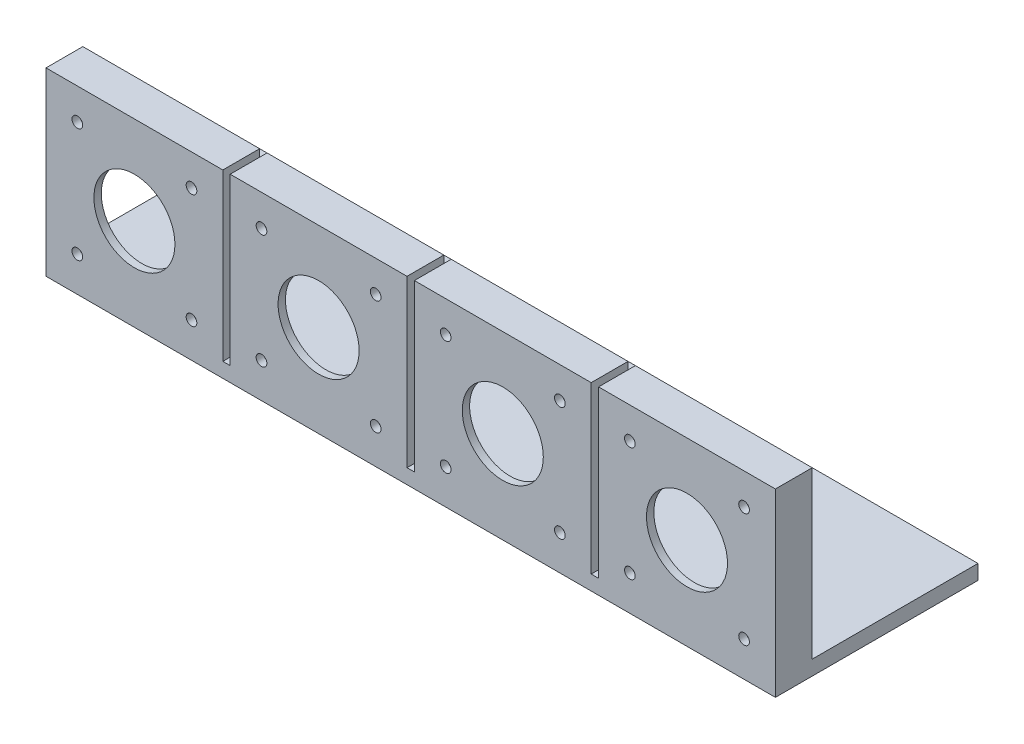
SolidWorks part; units mm, degrees
ref_plane "Спереди" through (0, 0, 0) normal (0, 0, 1) x (1, 0, 0)
ref_plane "Сверху" through (0, 0, 0) normal (0, 1, 0) x (1, 0, 0)
ref_plane "Справа" through (0, 0, 0) normal (1, 0, 0) x (0, 0, -1)
sketch "Эскиз1" plane through (0, 0, 0) normal (0, 0, 1) x (1, 0, 0)
  line L0 (-1000, 0) -> (49000, 0) construction
  line L1 (-21, -21) -> (21, -21)
  line L2 (-21, -21) -> (-21, 21)
  line L3 (-21, 21) -> (21, 21)
  line L4 (21, -21) -> (21, 21)
  line L5 (-21, -21) -> (21, 21) construction
  line L6 (-21, 21) -> (21, -21) construction
  line L7 (-24, -24) -> (24, -24)
  line L8 (-24, -24) -> (-24, 24)
  line L9 (-24, 24) -> (24, 24)
  line L10 (24, -24) -> (24, 24)
  line L11 (-24, -24) -> (24, 24) construction
  line L12 (-24, 24) -> (24, -24) construction
  line L13 (29, -21) -> (71, -21)
  line L14 (29, -21) -> (29, 21)
  line L15 (29, 21) -> (71, 21)
  line L16 (71, -21) -> (71, 21)
  line L17 (26, -24) -> (74, -24)
  line L18 (26, -24) -> (26, 24)
  line L19 (26, 24) -> (74, 24)
  line L20 (74, -24) -> (74, 24)
  line L21 (29, -21) -> (71, 21) construction
  line L22 (29, 21) -> (71, -21) construction
  line L23 (26, -24) -> (74, 24) construction
  line L24 (26, 24) -> (74, -24) construction
  line L25 (79, -21) -> (121, -21)
  line L26 (79, -21) -> (79, 21)
  line L27 (79, 21) -> (121, 21)
  line L28 (121, -21) -> (121, 21)
  line L29 (76, -24) -> (124, -24)
  line L30 (76, -24) -> (76, 24)
  line L31 (76, 24) -> (124, 24)
  line L32 (124, -24) -> (124, 24)
  line L33 (79, -21) -> (121, 21) construction
  line L34 (79, 21) -> (121, -21) construction
  line L35 (76, -24) -> (124, 24) construction
  line L36 (76, 24) -> (124, -24) construction
  line L37 (129, -21) -> (171, -21)
  line L38 (129, -21) -> (129, 21)
  line L39 (129, 21) -> (171, 21)
  line L40 (171, -21) -> (171, 21)
  line L41 (126, -24) -> (174, -24)
  line L42 (126, -24) -> (126, 24)
  line L43 (126, 24) -> (174, 24)
  line L44 (174, -24) -> (174, 24)
  line L45 (129, -21) -> (171, 21) construction
  line L46 (129, 21) -> (171, -21) construction
  line L47 (126, -24) -> (174, 24) construction
  line L48 (126, 24) -> (174, -24) construction
  point P0 (0, 0)
  point P5 (0, 0)
  point P14 (50, 0)
  point P19 (50, 0)
  point P24 (100, 0)
  point P29 (100, 0)
  point P34 (150, 0)
  point P39 (150, 0)
  dimension "D1" = 42
  dimension "D2" = 48
  dimension "D3" = 3
  dimension "D4" = 42
  dimension "D6" = 2
  dimension "D5" = 4
extrude "Бобышка-Вытянуть1" add sketch "Эскиз1" along normal blind 10
sketch "Эскиз2" plane through (0, 0, 10) normal (0, 0, 1) x (1, 0, 0)
  line L0 (-1000, 0) -> (49000, 0) construction
  line L1 (-21, 21) -> (21, 21)
  line L2 (-21, 21) -> (-21, -21)
  line L3 (-21, -21) -> (21, -21)
  line L4 (21, 21) -> (21, -21)
  line L5 (-21, 21) -> (21, -21) construction
  line L6 (-21, -21) -> (21, 21) construction
  line L7 (29, 21) -> (71, 21)
  line L8 (29, 21) -> (29, -21)
  line L9 (29, -21) -> (71, -21)
  line L10 (71, 21) -> (71, -21)
  line L11 (29, 21) -> (71, -21) construction
  line L12 (29, -21) -> (71, 21) construction
  line L13 (79, 21) -> (121, 21)
  line L14 (79, 21) -> (79, -21)
  line L15 (79, -21) -> (121, -21)
  line L16 (121, 21) -> (121, -21)
  line L17 (79, 21) -> (121, -21) construction
  line L18 (79, -21) -> (121, 21) construction
  line L19 (129, 21) -> (171, 21)
  line L20 (129, 21) -> (129, -21)
  line L21 (129, -21) -> (171, -21)
  line L22 (171, 21) -> (171, -21)
  line L23 (129, 21) -> (171, -21) construction
  line L24 (129, -21) -> (171, 21) construction
  circle A0 centre (-15.5, 15.5) radius 1.45
  circle A1 centre (15.5, 15.5) radius 1.45
  circle A2 centre (15.5, -15.5) radius 1.45
  circle A3 centre (-15.5, -15.5) radius 1.45
  circle A4 centre (34.5, 15.5) radius 1.45
  circle A5 centre (65.5, 15.5) radius 1.45
  circle A6 centre (65.5, -15.5) radius 1.45
  circle A7 centre (34.5, -15.5) radius 1.45
  circle A8 centre (84.5, 15.5) radius 1.45
  circle A9 centre (115.5, 15.5) radius 1.45
  circle A10 centre (115.5, -15.5) radius 1.45
  circle A11 centre (84.5, -15.5) radius 1.45
  circle A12 centre (134.5, 15.5) radius 1.45
  circle A13 centre (165.5, 15.5) radius 1.45
  circle A14 centre (165.5, -15.5) radius 1.45
  circle A15 centre (134.5, -15.5) radius 1.45
  circle A16 centre (0, 0) radius 11
  circle A17 centre (50, 0) radius 11
  circle A18 centre (100, 0) radius 11
  circle A19 centre (150, 0) radius 11
  point P4 (0, 0)
  point P12 (0, 0)
  point P15 (0, 0)
  point P18 (0, 0)
  point P21 (0, 0)
  point P27 (50, 0)
  point P30 (50, 0)
  point P33 (50, 0)
  point P36 (50, 0)
  point P39 (50, 0)
  point P44 (100, 0)
  point P47 (100, 0)
  point P50 (100, 0)
  point P53 (100, 0)
  point P56 (100, 0)
  point P61 (150, 0)
  point P64 (150, 0)
  point P67 (150, 0)
  point P70 (150, 0)
  point P73 (150, 0)
  dimension "D1" = 5.5
  dimension "D2" = 2.9
  dimension "D3" = 4
  dimension "D6" = 22
  dimension "D5" = 8
  dimension "D4" = 4
extrude "Бобышка-Вытянуть2" add sketch "Эскиз2" against normal blind 2
sketch "Эскиз3" plane through (0, -24, 0) normal (0, -1, 0) x (1, 0, 0)
  line L1 (-24, 10) -> (174, 10)
  line L2 (-24, 10) -> (-24, -45)
  line L4 (174, 10) -> (174, -45)
  line L5 (-24, 10) -> (174, -45) construction
  line L6 (-24, -45) -> (174, 10) construction
  line L7 (-24, -45) -> (174, -45)
  point P4 (75, -17.5)
  dimension "D1" = 198
  dimension "D2" = 55
extrude "Бобышка-Вытянуть3" add sketch "Эскиз3" along normal blind 1 and the other way blind 3
combine bodies "Соединить1" operation type add bodies to combine 108 109 110 111 103 107 106
